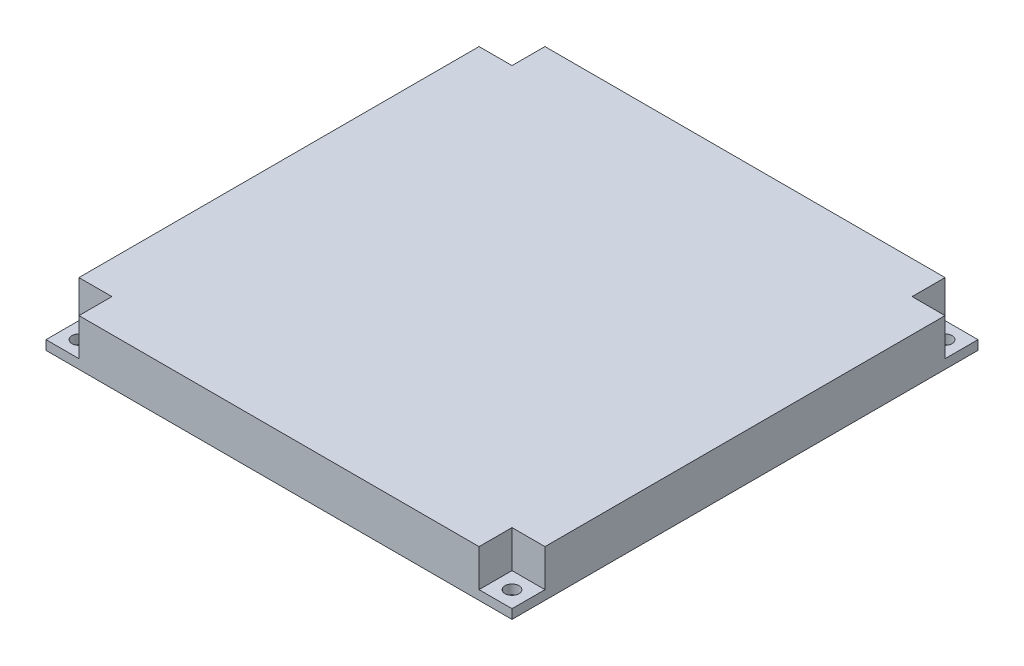
SolidWorks part; units mm, degrees
ref_plane "Alzado" through (0, 0, 0) normal (0, 0, 1) x (1, 0, 0)
ref_plane "Planta" through (0, 0, 0) normal (0, 1, 0) x (1, 0, 0)
ref_plane "Vista lateral" through (0, 0, 0) normal (1, 0, 0) x (0, 0, -1)
sketch "Croquis1" plane through (0, 0, 0) normal (0, 1, 0) x (1, 0, 0)
  line L1 (-50, 50) -> (50, 50)
  line L2 (-50, 50) -> (-50, -50)
  line L3 (-50, -50) -> (50, -50)
  line L4 (50, 50) -> (50, -50)
  line L5 (-50, 50) -> (50, -50) construction
  line L6 (-50, -50) -> (50, 50) construction
  point P0 (0, 0)
  dimension "D1" = 100
  dimension "D2" = 100
extrude "Saliente-Extruir1" add sketch "Croquis1" along normal blind 10
sketch "Croquis2" plane through (0, 10, 0) normal (0, 1, 0) x (1, 0, 0)
  line L0 (-50, -50) -> (50, 50) construction
  line L1 (-50, 50) -> (50, -50) construction
  circle A0 centre (-46.4645, -46.4645) radius 1.5
  circle A1 centre (-46.4645, 46.4645) radius 1.5
  circle A2 centre (46.4645, 46.4645) radius 1.5
  circle A3 centre (46.4645, -46.4645) radius 1.5
  point P19 (0, 0)
  dimension "D1" = 3
  dimension "D2" = 5
  dimension "D3" = 4
extrude "Cortar-Extruir1" cut sketch "Croquis2" against normal blind 30
sketch "Croquis3" plane through (0, 10, 0) normal (0, 1, 0) x (1, 0, 0)
  line L0 (-42.9289, 42.9289) -> (-50, 50) construction
  line L1 (-42.9289, -42.9289) -> (-50, -42.9289)
  line L2 (-42.9289, -42.9289) -> (-42.9289, -50)
  line L3 (-42.9289, -50) -> (-50, -50)
  line L4 (-50, -42.9289) -> (-50, -50)
  line L5 (-42.9289, -42.9289) -> (-50, -50) construction
  line L6 (-42.9289, -50) -> (-50, -42.9289) construction
  line L7 (-50, 42.9289) -> (-42.9289, 50) construction
  line L8 (-42.9289, 42.9289) -> (-50, 42.9289)
  line L9 (-42.9289, 42.9289) -> (-42.9289, 50)
  line L10 (-42.9289, 50) -> (-50, 50)
  line L11 (-50, 42.9289) -> (-50, 50)
  line L12 (42.9289, 42.9289) -> (50, 50) construction
  line L13 (42.9289, 50) -> (50, 42.9289) construction
  line L14 (42.9289, 42.9289) -> (42.9289, 50)
  line L15 (42.9289, 42.9289) -> (50, 42.9289)
  line L16 (50, 42.9289) -> (50, 50)
  line L17 (42.9289, 50) -> (50, 50)
  line L18 (42.9289, -42.9289) -> (50, -50) construction
  line L19 (50, -42.9289) -> (42.9289, -50) construction
  line L20 (42.9289, -42.9289) -> (50, -42.9289)
  line L21 (42.9289, -42.9289) -> (42.9289, -50)
  line L22 (42.9289, -50) -> (50, -50)
  line L23 (50, -42.9289) -> (50, -50)
  point P0 (-46.4645, -46.4645)
  point P10 (-46.4645, 46.4645)
  point P15 (46.4645, 46.4645)
  point P20 (46.4645, -46.4645)
  point P25 (0, 0)
  dimension "D1" = 4
extrude "Cortar-Extruir2" cut sketch "Croquis3" against normal blind 8
shell "Vaciado1" thickness 2 removed face at (46.4645, 0, 47.9645)
